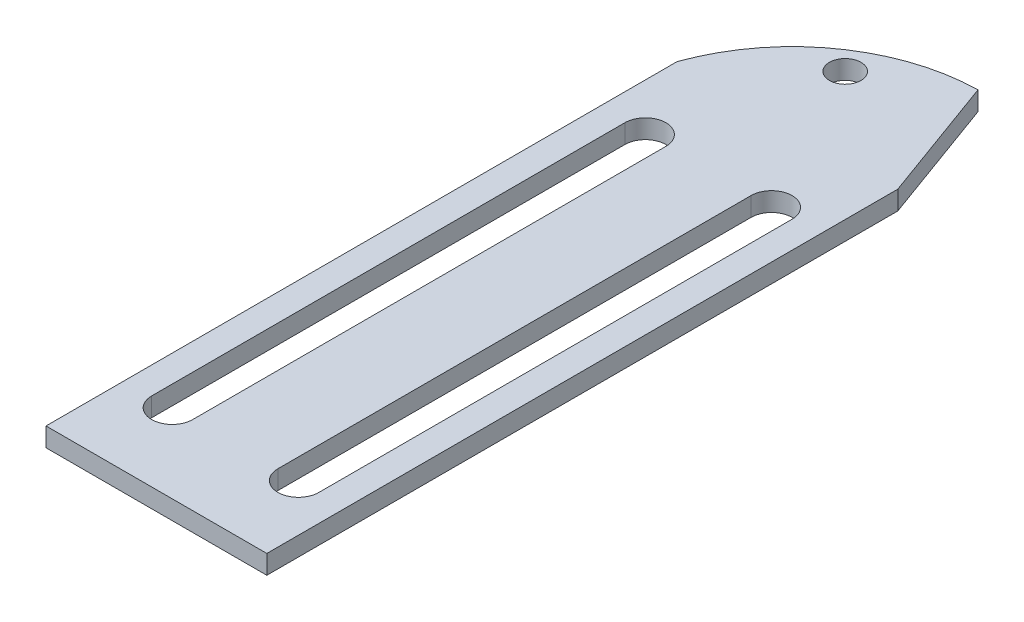
SolidWorks part; units mm, degrees
ref_plane "Front Plane" through (0, 0, 0) normal (0, 0, 1) x (1, 0, 0)
ref_plane "Top Plane" through (0, 0, 0) normal (0, 1, 0) x (1, 0, 0)
ref_plane "Right Plane" through (0, 0, 0) normal (1, 0, 0) x (0, 0, -1)
sketch "Sketch1" plane through (0, 0, 0) normal (0, 1, 0) x (1, 0, 0)
  line L0 (17.5, 50) -> (-17.5, 50)
  line L1 (-17.5, 50) -> (17.5, 50)
  line L2 (-17.5, 50) -> (-17.5, -50)
  line L3 (-17.5, -50) -> (17.5, -50)
  line L4 (17.5, 50) -> (17.5, -50)
  line L5 (0, -50) -> (0, 50) construction
  line L6 (-17.5, 0) -> (17.5, 0) construction
  line L7 (17.5, 50) -> (10.2206, 70)
  line L8 (-17.5, 50) -> (-24.7794, 70)
  line L9 (10.2206, 70) -> (-24.7794, 70)
  circle A0 centre (-2.8303, 62) radius 2.5
  point P0 (0, 0)
  dimension "D5" = 5
  dimension "D6" = 8
  dimension "D7" = 15
  dimension "D1" = 100
  dimension "D2" = 35
  dimension "D3" = 20
  dimension "D4" = 160
extrude "Boss-Extrude1" add sketch "Sketch1" along normal blind 3 contours L4 L0 L2 L3 | L7 L9 L8 L0 A0 region at (0, 0, 0) region at (0, 0, -50.4677)
sketch "Sketch2" plane through (0, 3, 0) normal (0, 1, 0) x (1, 0, 0)
  line L0 (-17.5, 50) -> (-17.5, -50) construction
  line L1 (-12.5, 30) -> (12.5, 30)
  line L2 (-12.5, 30) -> (-12.5, 0)
  line L3 (-12.5, 0) -> (12.5, 0)
  line L4 (12.5, 30) -> (12.5, 0)
  line L5 (0, 0) -> (0, 30) construction
  line L6 (-12.5, 15) -> (12.5, 15) construction
  line L7 (-12.5, -10) -> (12.5, -10)
  line L8 (-12.5, -10) -> (-12.5, -40)
  line L9 (-12.5, -40) -> (12.5, -40)
  line L10 (12.5, -10) -> (12.5, -40)
  line L11 (0, -40) -> (0, -10) construction
  line L12 (-12.5, -25) -> (12.5, -25) construction
  line L13 (17.5, 50) -> (17.5, -50) construction
  line L14 (-17.5, -50) -> (17.5, -50) construction
  circle A0 centre (-12.5, 30) radius 3.25
  circle A1 centre (12.5, 30) radius 3.25
  circle A2 centre (-12.5, 0) radius 3.25
  circle A3 centre (12.5, 0) radius 3.25
  circle A4 centre (12.5, -10) radius 3.25
  circle A5 centre (-12.5, -10) radius 3.25
  circle A6 centre (-12.5, -40) radius 3.25
  circle A7 centre (12.5, -40) radius 3.25
  point P0 (0, 15)
  point P4 (0, -25)
  dimension "D9" = 6.5
  dimension "D1" = 30
  dimension "D2" = 30
  dimension "D3" = 5
  dimension "D4" = 5
  dimension "D5" = 5
  dimension "D6" = 5
  dimension "D7" = 10
  dimension "D8" = 10
extrude "Cut-Extrude1" [suppressed] cut sketch "Sketch2" against normal through all both and the other way through all contours L4 A1 L1 | A0 | A1 | A3 | A2 | A5 | A4 | A6 | A7
sketch "Sketch3" plane through (0, 3, 0) normal (0, 1, 0) x (1, 0, 0)
  line L0 (-10, 0) -> (10, 0)
  line L1 (-10, -37.5) -> (-10, 37.5) construction
  line L2 (-13.25, -37.5) -> (-13.25, 37.5)
  line L3 (-6.75, -37.5) -> (-6.75, 37.5)
  line L4 (10, -37.5) -> (10, 37.5) construction
  line L5 (6.75, -37.5) -> (6.75, 37.5)
  line L6 (13.25, -37.5) -> (13.25, 37.5)
  arc A0 (-13.25, -37.5) -> (-6.75, -37.5) centre (-10, -37.5) ccw
  arc A1 (-6.75, 37.5) -> (-13.25, 37.5) centre (-10, 37.5) ccw
  arc A2 (6.75, -37.5) -> (13.25, -37.5) centre (10, -37.5) ccw
  arc A3 (13.25, 37.5) -> (6.75, 37.5) centre (10, 37.5) ccw
  point P4 (0, 0)
  point P7 (-10, 0)
  point P14 (10, 0)
  point P19 (-166.879, 62.5615)
  dimension "D1" = 20
  dimension "D2" = 6.5
  dimension "D4" = 75
extrude "Cut-Extrude2" cut sketch "Sketch3" against normal through all contours L3 A1 L2 A0 | L5 A3 L6 A2
fillet "Fillet1" radius 30 1 edges at (-24.7794, 1.5, -70)
